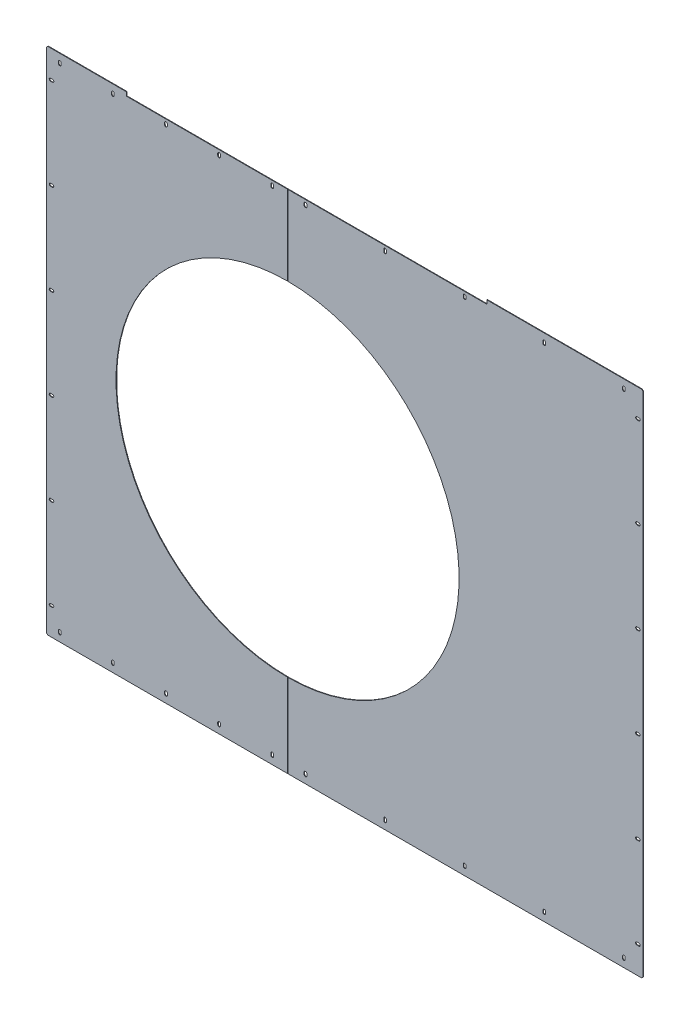
SolidWorks part; units mm, degrees
material "Q235-A"
ref_plane "前视基准面" through (0, 0, 0) normal (0, 0, 1) x (1, 0, 0)
ref_plane "上视基准面" through (0, 0, 0) normal (0, 1, 0) x (1, 0, 0)
ref_plane "右视基准面" through (0, 0, 0) normal (1, 0, 0) x (0, 0, -1)
sketch "草图1" plane through (0, 0, 0) normal (0, 0, 1) x (1, 0, 0)
  line L1 (786.5, -672.5) -> (-786.5, -672.5)
  line L2 (786.5, -672.5) -> (786.5, 672.5)
  line L3 (786.5, 672.5) -> (-786.5, 672.5)
  line L4 (-786.5, -672.5) -> (-786.5, 672.5)
  line L5 (786.5, -672.5) -> (-786.5, 672.5) construction
  line L6 (786.5, 672.5) -> (-786.5, -672.5) construction
  point P0 (0, 0)
  dimension "D1" = 1345
  dimension "D2" = 1573
base flange "基体-法兰1" sketch "草图1" thickness 1.5 reverse thickness direction no parameters "D1"=0.7366
sketch "草图4" plane through (0, 0, -1.5) normal (0, 0, -1) x (-1, 0, 0)
  circle A0 centre (150.7663, 0) radius 452.5
  dimension "D1" = 905
extrude "切除-拉伸1" cut sketch "草图4" against normal blind 10 normal cut yes
sketch "草图5" plane through (0, 0, 0) normal (0, 0, 1) x (1, 0, 0)
  line L1 (-150.2663, -773.7286) -> (-151.2663, -773.7286)
  line L2 (-150.2663, -773.7286) -> (-150.2663, 773.7285)
  line L3 (-150.2663, 773.7285) -> (-151.2663, 773.7285)
  line L4 (-151.2663, -773.7286) -> (-151.2663, 773.7285)
  line L5 (-150.2663, -773.7286) -> (-151.2663, 773.7285) construction
  line L6 (-150.2663, 773.7285) -> (-151.2663, -773.7286) construction
  point P0 (-150.7663, 0)
  dimension "D1" = 1
extrude "切除-拉伸2" cut sketch "草图5" against normal blind 10 normal cut yes
chamfer "倒角1" distance 3 angle 45 2 edges at (-786.5, -672.5, -0.75) (-786.5, 672.5, -0.75)
chamfer "倒角2" distance 3 angle 45 2 edges at (786.5, 672.5, -0.75) (786.5, -672.5, -0.75)
sketch "草图10" plane through (0, 0, 0) normal (0, 0, 1) x (1, 0, 0)
  line L0 (-751.5, 647.5) -> (-751.5, 652.5) construction
  line L1 (-755, 647.5) -> (-755, 652.5)
  line L2 (-748, 647.5) -> (-748, 652.5)
  line L3 (-151.2663, 672.5) -> (-783.5, 672.5) construction
  line L4 (-786.5, 669.5) -> (-786.5, -669.5) construction
  line L5 (-751.5, -652.5) -> (-751.5, -647.5) construction
  line L6 (-755, -652.5) -> (-755, -647.5)
  line L7 (-748, -652.5) -> (-748, -647.5)
  line L8 (-783.5, -672.5) -> (-151.2663, -672.5) construction
  arc A0 (-755, 647.5) -> (-748, 647.5) centre (-751.5, 647.5) ccw
  arc A1 (-748, 652.5) -> (-755, 652.5) centre (-751.5, 652.5) ccw
  arc A2 (-755, -652.5) -> (-748, -652.5) centre (-751.5, -652.5) ccw
  arc A3 (-748, -647.5) -> (-755, -647.5) centre (-751.5, -647.5) ccw
  point P2 (-751.5, 650)
  point P13 (-751.5, -650)
  dimension "D1" = 7
  dimension "D2" = 5
  dimension "D3" = 22.5
  dimension "D4" = 35
  dimension "D5" = 7
  dimension "D6" = 5
  dimension "D7" = 22.5
extrude "切除-拉伸3" cut sketch "草图10" against normal blind 10
pattern_linear "阵列(线性)1" count 5 spacing 140 along (1, 0, 0) of "切除-拉伸3"
sketch "草图12" plane through (0, 0, 0) normal (0, 0, 1) x (1, 0, 0)
  line L0 (-776, 600) -> (-771, 600) construction
  line L1 (-776, 603.5) -> (-771, 603.5)
  line L2 (-776, 596.5) -> (-771, 596.5)
  line L3 (-151.2663, 672.5) -> (-783.5, 672.5) construction
  line L4 (-786.5, 669.5) -> (-786.5, -669.5) construction
  arc A0 (-776, 603.5) -> (-776, 596.5) centre (-776, 600) ccw
  arc A1 (-771, 596.5) -> (-771, 603.5) centre (-771, 600) ccw
  point P2 (-773.5, 600)
  dimension "D1" = 72.5
  dimension "D2" = 7
  dimension "D3" = 5
  dimension "D4" = 13
extrude "切除-拉伸4" cut sketch "草图12" against normal blind 10
pattern_linear "阵列(线性)2" count 6 spacing 240 along (0, -1, 0) of "切除-拉伸4"
sketch "草图13" plane through (0, 0, 0) normal (0, 0, 1) x (1, 0, 0)
  line L0 (771, 600) -> (776, 600) construction
  line L1 (771, 603.5) -> (776, 603.5)
  line L2 (771, 596.5) -> (776, 596.5)
  line L3 (786.5, -669.5) -> (786.5, 669.5) construction
  line L4 (783.5, 672.5) -> (-150.2663, 672.5) construction
  arc A0 (771, 603.5) -> (771, 596.5) centre (771, 600) ccw
  arc A1 (776, 596.5) -> (776, 603.5) centre (776, 600) ccw
  point P2 (773.5, 600)
  dimension "D1" = 7
  dimension "D2" = 5
  dimension "D3" = 13
  dimension "D4" = 72.5
extrude "切除-拉伸5" cut sketch "草图13" against normal blind 10
pattern_linear "阵列(线性)3" count 6 spacing 240 along (0, -1, 0) of "切除-拉伸5"
sketch "草图14" plane through (0, 0, 0) normal (0, 0, 1) x (1, 0, 0)
  line L0 (736.5, 652.5) -> (736.5, 647.5) construction
  line L1 (740, 652.5) -> (740, 647.5)
  line L2 (733, 652.5) -> (733, 647.5)
  line L3 (783.5, 672.5) -> (-150.2663, 672.5) construction
  line L4 (786.5, -669.5) -> (786.5, 669.5) construction
  line L5 (736.5, -652.5) -> (736.5, -647.5) construction
  line L6 (733, -652.5) -> (733, -647.5)
  line L7 (740, -652.5) -> (740, -647.5)
  line L8 (-150.2663, -672.5) -> (783.5, -672.5) construction
  arc A0 (740, 652.5) -> (733, 652.5) centre (736.5, 652.5) ccw
  arc A1 (733, 647.5) -> (740, 647.5) centre (736.5, 647.5) ccw
  arc A2 (733, -652.5) -> (740, -652.5) centre (736.5, -652.5) ccw
  arc A3 (740, -647.5) -> (733, -647.5) centre (736.5, -647.5) ccw
  point P2 (736.5, 650)
  point P12 (736.5, -650)
  dimension "D1" = 7
  dimension "D2" = 5
  dimension "D3" = 22.5
  dimension "D4" = 50
  dimension "D5" = 7
  dimension "D6" = 5
  dimension "D7" = 22.5
extrude "切除-拉伸6" cut sketch "草图14" against normal blind 10
pattern_linear "阵列(线性)4" count 5 spacing 210 along (-1, 0, 0) of "切除-拉伸6"
sketch "草图15" plane through (0, 0, -1.5) normal (0, 0, -1) x (-1, 0, 0)
  line L1 (151.2663, 672.5) -> (576.2663, 672.5)
  line L2 (151.2663, 672.5) -> (151.2663, 662.5)
  line L3 (151.2663, 662.5) -> (576.2663, 662.5)
  line L4 (576.2663, 672.5) -> (576.2663, 662.5)
  dimension "D1" = 10
  dimension "D2" = 425
extrude "切除-拉伸7" cut sketch "草图15" against normal blind 10
sketch "草图16" plane through (0, 0, -1.5) normal (0, 0, -1) x (-1, 0, 0)
  line L1 (150.2663, 672.5) -> (-374.7337, 672.5)
  line L2 (150.2663, 672.5) -> (150.2663, 662.5)
  line L3 (150.2663, 662.5) -> (-374.7337, 662.5)
  line L4 (-374.7337, 672.5) -> (-374.7337, 662.5)
  dimension "D1" = 10
  dimension "D2" = 525
extrude "切除-拉伸8" cut sketch "草图16" against normal blind 10
sketch "折弯-线1" [suppressed] plane through (0, 0, 0) normal (0, 1, 0) x (1, 0, 0)
sketch "边界框1" [suppressed] plane through (0, 0, 0) normal (0, 1, 0) x (1, 0, 0)
sheet metal parameters "钣金1" thickness 1.5 parameters "D1"=0.7366
flat pattern "平板型式1" [suppressed]
sketch "折弯-线2" plane through (0, 0, 0) normal (0, 1, 0) x (1, 0, 0)
sketch3d "边界框2" [suppressed]
  line L0 (-786.5, -672.5, 0) -> (786.5, -672.5, 0) construction
  line L1 (-786.5, 672.5, 0) -> (786.5, 672.5, 0) construction
  line L2 (-786.5, -672.5, 0) -> (-786.5, 672.5, 0) construction
  line L3 (786.5, -672.5, 0) -> (786.5, 672.5, 0) construction
sketch "草图2-1" [suppressed] plane through (0, 0, -1.5) normal (0, 0, -1) x (-1, 0, 0)
  circle A0 centre (152.2663, 0) radius 4.75
  dimension "D1" = 9.5
sheet metal parameters "钣金5" thickness 1.5 parameters "D1"=0.7366
flat pattern "平板型式1"
sketch "折弯-线2" plane through (0, 0, 0) normal (0, 1, 0) x (1, 0, 0)
sketch3d "边界框2" [suppressed]
  line L0 (-786.5, -672.5, 0) -> (786.5, -672.5, 0) construction
  line L1 (-786.5, 672.5, 0) -> (786.5, 672.5, 0) construction
  line L2 (-786.5, -672.5, 0) -> (-786.5, 672.5, 0) construction
  line L3 (786.5, -672.5, 0) -> (786.5, 672.5, 0) construction
sheet metal parameters "钣金6" thickness 1.5 parameters "D1"=0.7366
flat pattern "平板型式6"
sketch "折弯-线3" plane through (0, 0, 0) normal (0, 1, 0) x (1, 0, 0)
sketch3d "边界框3" [suppressed]
  line L0 (786.5, 672.5, 0) -> (786.5, -672.5, 0) construction
  line L1 (-150.2663, 672.5, 0) -> (-150.2663, -672.5, 0) construction
  line L2 (786.5, 672.5, 0) -> (-150.2663, 672.5, 0) construction
  line L3 (786.5, -672.5, 0) -> (-150.2663, -672.5, 0) construction
sheet metal parameters "钣金7" thickness 1.5 parameters "D1"=0.7366
flat pattern "平板型式7"
sketch "折弯-线4" plane through (0, 0, 0) normal (0, 1, 0) x (1, 0, 0)
sketch3d "边界框4" [suppressed]
  line L0 (-151.2663, 672.5, 0) -> (-151.2663, -672.5, 0) construction
  line L1 (-786.5, 672.5, 0) -> (-786.5, -672.5, 0) construction
  line L2 (-151.2663, 672.5, 0) -> (-786.5, 672.5, 0) construction
  line L3 (-151.2663, -672.5, 0) -> (-786.5, -672.5, 0) construction
sheet metal parameters "钣金8" thickness 1.5 parameters "D1"=0.7366
flat pattern "平板型式7"
sketch "折弯-线4" plane through (0, 0, 0) normal (0, 1, 0) x (1, 0, 0)
sketch3d "边界框4" [suppressed]
  line L0 (-151.2663, 672.5, 0) -> (-151.2663, -672.5, 0) construction
  line L1 (-786.5, 672.5, 0) -> (-786.5, -672.5, 0) construction
  line L2 (-151.2663, 672.5, 0) -> (-786.5, 672.5, 0) construction
  line L3 (-151.2663, -672.5, 0) -> (-786.5, -672.5, 0) construction
sheet metal parameters "钣金9" thickness 1.5 parameters "D1"=0.7366
flat pattern "平板型式7"
sketch "折弯-线4" plane through (0, 0, 0) normal (0, 1, 0) x (1, 0, 0)
sketch3d "边界框4" [suppressed]
  line L0 (-151.2663, 672.5, 0) -> (-151.2663, -672.5, 0) construction
  line L1 (-786.5, 672.5, 0) -> (-786.5, -672.5, 0) construction
  line L2 (-151.2663, 672.5, 0) -> (-786.5, 672.5, 0) construction
  line L3 (-151.2663, -672.5, 0) -> (-786.5, -672.5, 0) construction
sheet metal parameters "钣金10" thickness 1.5 parameters "D1"=0.7366
flat pattern "平板型式7"
sketch "折弯-线4" plane through (0, 0, 0) normal (0, 1, 0) x (1, 0, 0)
sketch3d "边界框4" [suppressed]
  line L0 (-151.2663, 672.5, 0) -> (-151.2663, -672.5, 0) construction
  line L1 (-786.5, 672.5, 0) -> (-786.5, -672.5, 0) construction
  line L2 (-151.2663, 672.5, 0) -> (-786.5, 672.5, 0) construction
  line L3 (-151.2663, -672.5, 0) -> (-786.5, -672.5, 0) construction
sheet metal parameters "钣金11" thickness 1.5 parameters "D1"=0.7366
flat pattern "平板型式7"
sketch "折弯-线4" plane through (0, 0, 0) normal (0, 1, 0) x (1, 0, 0)
sketch3d "边界框4" [suppressed]
  line L0 (-151.2663, 672.5, 0) -> (-151.2663, -672.5, 0) construction
  line L1 (-786.5, 672.5, 0) -> (-786.5, -672.5, 0) construction
  line L2 (-151.2663, 672.5, 0) -> (-786.5, 672.5, 0) construction
  line L3 (-151.2663, -672.5, 0) -> (-786.5, -672.5, 0) construction
sheet metal parameters "钣金12" thickness 1.5 parameters "D1"=0.7366
flat pattern "平板型式6"
sketch "折弯-线3" plane through (0, 0, 0) normal (0, 1, 0) x (1, 0, 0)
sketch3d "边界框3" [suppressed]
  line L0 (786.5, 672.5, 0) -> (786.5, -672.5, 0) construction
  line L1 (-150.2663, 672.5, 0) -> (-150.2663, -672.5, 0) construction
  line L2 (786.5, 672.5, 0) -> (-150.2663, 672.5, 0) construction
  line L3 (786.5, -672.5, 0) -> (-150.2663, -672.5, 0) construction
sheet metal parameters "钣金13" thickness 1.5 parameters "D1"=0.7366
flat pattern "平板型式6"
sketch "折弯-线3" plane through (0, 0, 0) normal (0, 1, 0) x (1, 0, 0)
sketch3d "边界框3" [suppressed]
  line L0 (786.5, 672.5, 0) -> (786.5, -672.5, 0) construction
  line L1 (-150.2663, 672.5, 0) -> (-150.2663, -672.5, 0) construction
  line L2 (786.5, 672.5, 0) -> (-150.2663, 672.5, 0) construction
  line L3 (786.5, -672.5, 0) -> (-150.2663, -672.5, 0) construction
sheet metal parameters "钣金14" thickness 1.5 parameters "D1"=0.7366
flat pattern "平板型式6"
sketch "折弯-线3" plane through (0, 0, 0) normal (0, 1, 0) x (1, 0, 0)
sketch3d "边界框3" [suppressed]
  line L0 (786.5, 672.5, 0) -> (786.5, -672.5, 0) construction
  line L1 (-150.2663, 672.5, 0) -> (-150.2663, -672.5, 0) construction
  line L2 (786.5, 672.5, 0) -> (-150.2663, 672.5, 0) construction
  line L3 (786.5, -672.5, 0) -> (-150.2663, -672.5, 0) construction
sheet metal parameters "钣金15" thickness 1.5 parameters "D1"=0.7366
flat pattern "平板型式6"
sketch "折弯-线3" plane through (0, 0, 0) normal (0, 1, 0) x (1, 0, 0)
sketch3d "边界框3" [suppressed]
  line L0 (786.5, 672.5, 0) -> (786.5, -672.5, 0) construction
  line L1 (-150.2663, 672.5, 0) -> (-150.2663, -672.5, 0) construction
  line L2 (786.5, 672.5, 0) -> (-150.2663, 672.5, 0) construction
  line L3 (786.5, -672.5, 0) -> (-150.2663, -672.5, 0) construction
sheet metal parameters "钣金16" thickness 1.5 parameters "D1"=0.7366
flat pattern "平板型式7"
sketch "折弯-线4" plane through (0, 0, 0) normal (0, 1, 0) x (1, 0, 0)
sketch3d "边界框4" [suppressed]
  line L0 (-151.2663, 672.5, 0) -> (-151.2663, -672.5, 0) construction
  line L1 (-786.5, 672.5, 0) -> (-786.5, -672.5, 0) construction
  line L2 (-151.2663, 672.5, 0) -> (-786.5, 672.5, 0) construction
  line L3 (-151.2663, -672.5, 0) -> (-786.5, -672.5, 0) construction
sheet metal parameters "钣金17" thickness 1.5 parameters "D1"=0.7366
flat pattern "平板型式6"
sketch "折弯-线3" plane through (0, 0, 0) normal (0, 1, 0) x (1, 0, 0)
sketch3d "边界框3" [suppressed]
  line L0 (786.5, 672.5, 0) -> (786.5, -672.5, 0) construction
  line L1 (-150.2663, 672.5, 0) -> (-150.2663, -672.5, 0) construction
  line L2 (786.5, 672.5, 0) -> (-150.2663, 672.5, 0) construction
  line L3 (786.5, -672.5, 0) -> (-150.2663, -672.5, 0) construction
